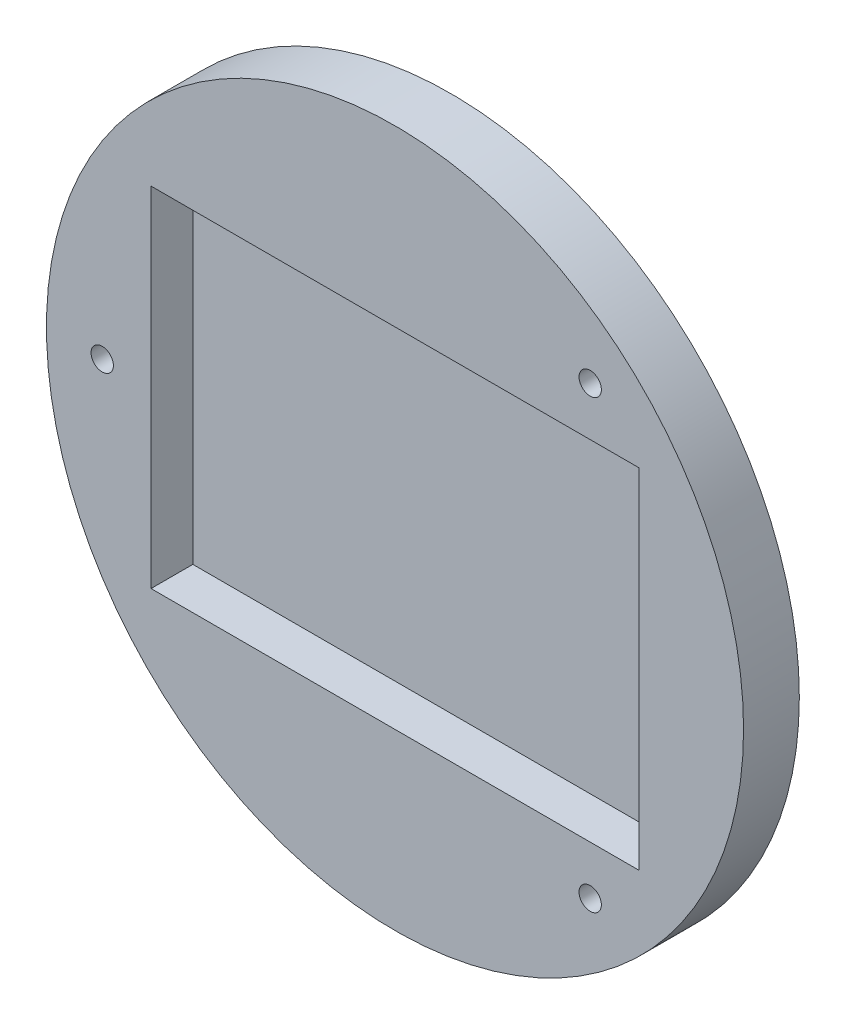
SolidWorks part; units mm, degrees
material "Nylon 101"
ref_plane "Front Plane" through (0, 0, 0) normal (0, 0, 1) x (1, 0, 0)
ref_plane "Top Plane" through (0, 0, 0) normal (0, 1, 0) x (1, 0, 0)
ref_plane "Right Plane" through (0, 0, 0) normal (1, 0, 0) x (0, 0, -1)
sketch "Sketch1" plane through (0, 0, 0) normal (0, 0, 1) x (1, 0, 0)
  line L1 (-18.5, 13.5) -> (18.5, 13.5)
  line L2 (-18.5, 13.5) -> (-18.5, -13.5)
  line L3 (-18.5, -13.5) -> (18.5, -13.5)
  line L4 (18.5, 13.5) -> (18.5, -13.5)
  line L5 (-18.5, 13.5) -> (18.5, -13.5) construction
  line L6 (-18.5, -13.5) -> (18.5, 13.5) construction
  line L7 (-17.5, 12.5) -> (17.5, 12.5)
  line L8 (-17.5, 12.5) -> (-17.5, -12.5)
  line L9 (-17.5, -12.5) -> (17.5, -12.5)
  line L10 (17.5, 12.5) -> (17.5, -12.5)
  line L11 (-17.5, 12.5) -> (17.5, -12.5) construction
  line L12 (-17.5, -12.5) -> (17.5, 12.5) construction
  circle A0 centre (0, 0) radius 25
  point P4 (0, 0)
  point P9 (0, 0)
  dimension "D1" = 50
  dimension "D2" = 27
  dimension "D3" = 37
  dimension "D4" = 1
  dimension "D5" = 1
extrude "Boss-Extrude1" add sketch "Sketch1" along normal blind 4 contours A0 L1 L4 L3 L2 | L4 L1 L2 L3 L7 L10 L9 L8 region at (0, 13.042, 0) region at (-24.2929, 0, 0)
extrude "Boss-Extrude2" add sketch "Sketch1<3>" along normal blind 1 contours L10 L7 L8 L9 region at (0, 0, 0)
sketch "Sketch1<3>" plane through (0, 0, 0) normal (0, 0, 1) x (1, 0, 0) same geometry as "Sketch1"
sketch "Sketch2" plane through (0, 0, 0) normal (0, 1, 0) x (1, 0, 0)
  line L4 (0, 15) -> (0, -15) construction
  line L5 (0, 6.5) -> (0, 0)
  line L6 (0, 0) -> (-6.5, 0)
  arc A1 (0, 6.5) -> (-6.5, 0) centre (0, 0) ccw
  dimension "D1" = 13
  dimension "D4" = 30
revolve "Revolve1" add sketch "Sketch2" angle 360 about L4
hole_wizard "M2x0.4 Tapped Hole1" positions "Sketch3" profile "Sketch4" tap size "M2x0.4" standard "ANSI Metric" end condition through all
sketch "Sketch3" plane through (0, 0, 4) normal (0, 0, 1) x (1, 0, 0)
  line L0 (-17.5, 12.5) -> (-17.5, -12.5) construction
  line L1 (-17.5, -12.5) -> (17.5, -12.5) construction
  line L2 (-17.5, 12.5) -> (17.5, 12.5) construction
  line L3 (17.5, 12.5) -> (17.5, -12.5) construction
  point P0 (-21, 0)
  point P2 (14, -16)
  point P4 (14, 16)
  dimension "D1" = 3.5
  dimension "D2" = 3.5
  dimension "D3" = 3.5
  dimension "D4" = 3.5
sketch "Sketch4" plane through (-21, 0, 4) normal (1, 0, 0) x (0, -1, 0)
  line L0 (0, 0) -> (0, 10.5)
  line L1 (0, 10.5) -> (0.8, 10.5)
  line L2 (0.8, 10.5) -> (0.8, 0)
  line L5 (0.8, 0) -> (0, 0)
  line L11 (0, -6.35) -> (0, 107.95) construction
  dimension "Thru Tap Drill Dia." = 1.6
  dimension "Thru Tap Drill Depth" = 10.5
cosmetic thread "Hole Thread1" parameters "D2"=2
cosmetic thread "Hole Thread2" parameters "D2"=2
cosmetic thread "Hole Thread3" parameters "D2"=2
